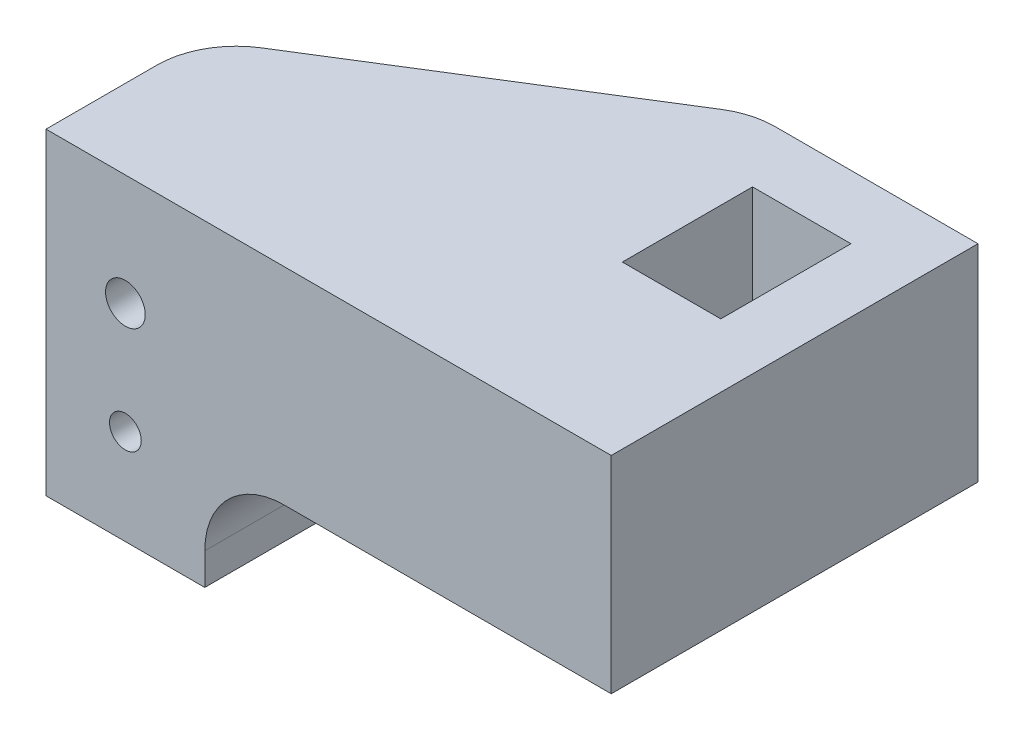
SolidWorks part; units mm, degrees
ref_plane "Plan de face" through (0, 0, 0) normal (0, 0, 1) x (1, 0, 0)
ref_plane "Plan de dessus" through (0, 0, 0) normal (0, 1, 0) x (1, 0, 0)
ref_plane "Plan de droite" through (0, 0, 0) normal (1, 0, 0) x (0, 0, -1)
sketch "Esquisse1" plane through (0, 0, 0) normal (0, 1, 0) x (1, 0, 0)
  line L0 (0, 0) -> (-56, 0) construction
  line L1 (0, 0) -> (0, 16.9732) construction
  line L2 (-32.5, 10) -> (0, 10) construction
  circle A0 centre (-56, 0) radius 3.5 construction
  circle A1 centre (56, 0) radius 3.5 construction
  circle A2 centre (-32.5, 10) radius 3.5 construction
  circle A3 centre (32.5, 10) radius 3.5 construction
  point P12 (0, 0)
  dimension "D1" = 7
  dimension "D3" = 7
  dimension "D2" = 112
  dimension "D4" = 65
  dimension "D5" = 10
sketch "Esquisse2" plane through (0, 0, 0) normal (0, 1, 0) x (1, 0, 0)
  line L0 (-35.6, 14.1) -> (-29.4, 5.9) construction
  line L1 (-35.6, 14.1) -> (-29.4, 14.1)
  line L2 (-35.6, 14.1) -> (-35.6, 5.9)
  line L3 (-35.6, 5.9) -> (-29.4, 5.9)
  line L4 (-29.4, 14.1) -> (-29.4, 5.9)
  line L5 (-29.4, 14.1) -> (-35.6, 5.9) construction
  line L6 (-61, -5) -> (-51.5843, -5)
  line L7 (-51.5843, -5) -> (-25.4, -5)
  line L8 (-25.4, -5) -> (-25.4, 18.1)
  line L9 (-25.4, 18.1) -> (-39.6, 18.1)
  line L10 (-39.6, 18.1) -> (-61, 4.7503)
  line L11 (-61, 4.7503) -> (-61, -5)
  point P4 (-24.318, 14.9899)
  point P5 (-32.5, 10)
  point P13 (-36.9704, 16.3434)
  dimension "D1" = 6.2
  dimension "D2" = 8.2
  dimension "D3" = 5
  dimension "D4" = 5
  dimension "D5" = 4
  dimension "D6" = 4
  dimension "D7" = 4
extrude "Boss.-Extru.1" add sketch "Esquisse2" along normal blind 20
sketch "Esquisse3" plane through (0, 0, 5) normal (0, 0, 1) x (1, 0, 0)
  line L0 (-56, 0) -> (-56, 20) construction
  line L1 (-52.5, 0) -> (-59.5, 0) construction
  line L2 (-61, 20) -> (-25.4, 20) construction
  line L3 (-56, 10) -> (-61, 10) construction
  line L4 (-61, 20) -> (-61, 0) construction
  line L5 (-25.4, 20) -> (-25.4, 0) construction
  line L6 (-51, 0) -> (-25.4, 0)
  line L7 (-51, 0) -> (-51, 7)
  line L8 (-51, 7) -> (-25.4, 7)
  line L9 (-25.4, 0) -> (-25.4, 7)
  circle A0 centre (-56, 12.9999) radius 1.25
  circle A1 centre (-56, 5.9999) radius 1
  dimension "D1" = 2
  dimension "D2" = 2.5
  dimension "D3" = 7
  dimension "D4" = 7
  dimension "D5" = 10
extrude "Enlèv. mat.-Extru.1" cut sketch "Esquisse3" against normal through all
fillet "Congé1" radius 5 1 edges at (-51, 7, -2.9942)
fillet "Congé2" radius 5 2 edges at (-39.6, 13.5, -18.1) (-61, 10, -4.7503)
